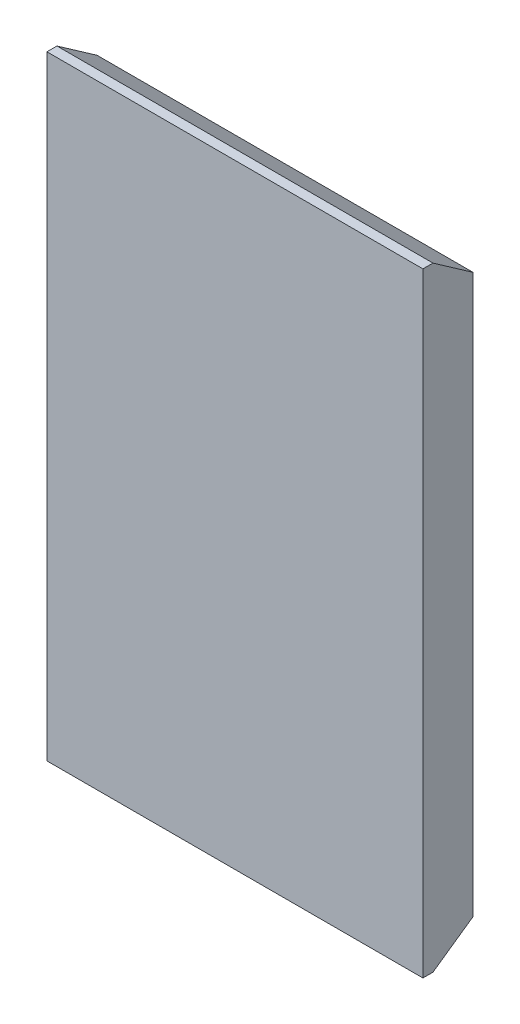
SolidWorks part; units mm, degrees
note: The reader was unsure of these and kept them because the rebuilt part matched: thickness of "基体-法兰1", "钣金6".
ref_plane "前视基准面" through (0, 0, 0) normal (0, 0, 1) x (1, 0, 0)
ref_plane "上视基准面" through (0, 0, 0) normal (0, 1, 0) x (1, 0, 0)
ref_plane "右视基准面" through (0, 0, 0) normal (1, 0, 0) x (0, 0, -1)
sketch "草图1" plane through (0, 0, 0) normal (0, 0, 1) x (1, 0, 0)
  line L1 (-75, 122.5) -> (75, 122.5)
  line L2 (-75, 122.5) -> (-75, -122.5)
  line L3 (-75, -122.5) -> (75, -122.5)
  line L4 (75, 122.5) -> (75, -122.5)
  line L5 (-75, 122.5) -> (75, -122.5) construction
  line L6 (-75, -122.5) -> (75, 122.5) construction
  point P0 (0, 0)
  dimension "D1" = 150
  dimension "D2" = 245
base flange "基体-法兰1" sketch "草图1" thickness 20 reverse thickness direction no parameters "D1"=1
chamfer "倒角1" distance 16 angle 35 1 edges at (0, 122.5, -20) first distance on face at (0, 122.5, -10)
chamfer "倒角2" distance 16 angle 35 1 edges at (0, -122.5, -20) first distance on face at (0, -122.5, -10)
sketch "折弯-线1" plane through (0, 0, 0) normal (0, 1, 0) x (1, 0, 0)
sketch "边界框1" plane through (0, 0, 0) normal (0, 1, 0) x (1, 0, 0)
sheet metal parameters "钣金6" thickness 20 parameters "D1"=1, "D7"=10
flat pattern "平板型式6" [suppressed]
sketch "折弯-线2" plane through (0, 0, 0) normal (0, 1, 0) x (1, 0, 0)
sketch "边界框2" [suppressed] plane through (0, 0, 0) normal (0, 1, 0) x (1, 0, 0)
